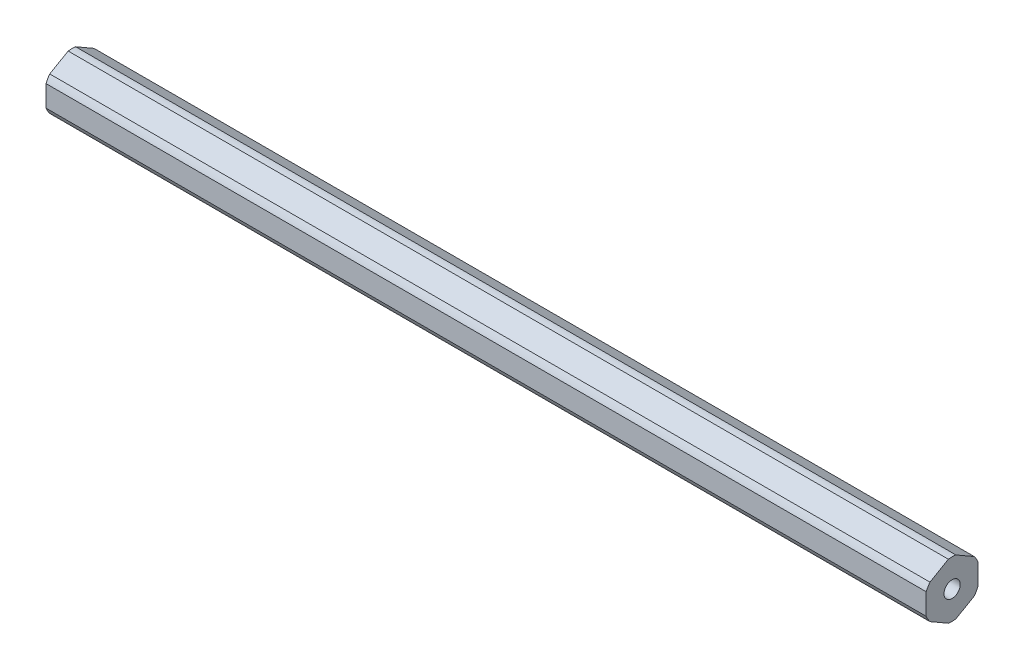
SolidWorks part; units mm, degrees
material "6061 Alloy"
ref_plane "Front Plane" through (0, 0, 0) normal (0, 0, 1) x (1, 0, 0)
ref_plane "Top Plane" through (0, 0, 0) normal (0, 1, 0) x (1, 0, 0)
ref_plane "Right Plane" through (0, 0, 0) normal (1, 0, 0) x (0, 0, -1)
ref_plane "Plane1" through (914.4, 0, 0) normal (1, 0, 0) x (0, 0, -1)
sketch "Sketch1" plane through (914.4, 0, 0) normal (1, 0, 0) x (0, 0, -1)
  line L0 (-5.4343, -4.1949) -> (-0.9157, -6.8037)
  line L1 (0.9157, -6.8037) -> (5.4343, -4.1949)
  line L2 (6.35, -2.6088) -> (6.35, 2.6088)
  line L3 (5.4343, 4.1949) -> (0.9157, 6.8037)
  line L4 (-0.9157, 6.8037) -> (-5.4343, 4.1949)
  line L5 (-6.35, 2.6088) -> (-6.35, -2.6088)
  circle A0 centre (0, 0) radius 1.9939
  arc A1 (-6.35, -2.6088) -> (-5.4343, -4.1949) centre (0, 0) ccw
  arc A2 (-0.9157, -6.8037) -> (0.9157, -6.8037) centre (0, 0) ccw
  arc A3 (5.4343, -4.1949) -> (6.35, -2.6088) centre (0, 0) ccw
  arc A4 (6.35, 2.6088) -> (5.4343, 4.1949) centre (0, 0) ccw
  arc A5 (0.9157, 6.8037) -> (-0.9157, 6.8037) centre (0, 0) ccw
  arc A6 (-5.4343, 4.1949) -> (-6.35, 2.6088) centre (0, 0) ccw
extrude "Boss-Extrude1" add sketch "Sketch1" against normal blind 215.9
equation "\"Hex Length\"= 8.5in"
equation "\"D1@Boss-Extrude1\"=\"Hex Length\""
